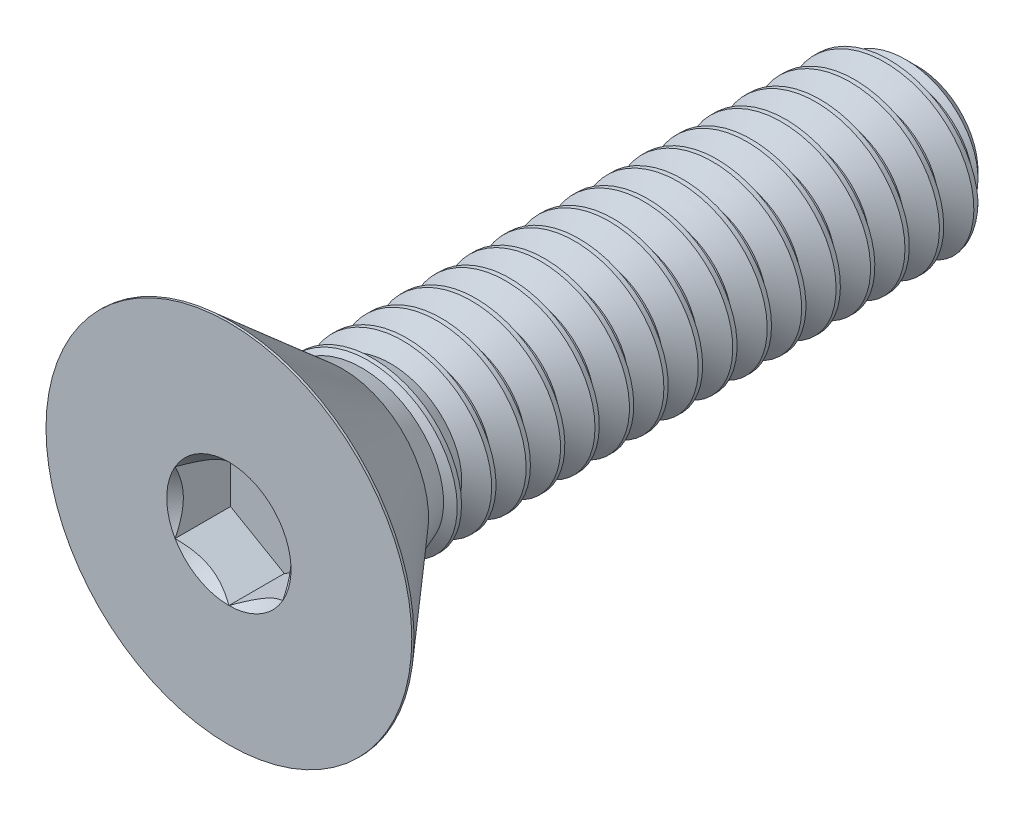
SolidWorks part; units mm, degrees
material "Plain Carbon Steel"
ref_plane "Front Plane" through (0, 0, 0) normal (0, 0, 1) x (1, 0, 0)
ref_plane "Top Plane" through (0, 0, 0) normal (0, 1, 0) x (1, 0, 0)
ref_plane "Right Plane" through (0, 0, 0) normal (1, 0, 0) x (0, 0, -1)
sketch "Sketch1" plane through (0, 0, 0) normal (1, 0, 0) x (0, 0, -1)
  line L0 (-12.7, 0) -> (12.7, 0) construction
  line L1 (-12.7, 0) -> (-12.7, 6.7437)
  line L2 (-12.7, 6.7437) -> (-12.6182, 6.7437)
  line L3 (-12.6182, 6.7437) -> (-8.6106, 3.2599)
  line L4 (-12.6182, -6.7437) -> (-8.6106, -3.2599)
  line L5 (12.7, 0) -> (12.7, 3.175)
  line L6 (12.7, 3.175) -> (-8.6106, 3.175)
  line L7 (11.7475, 3.175) -> (12.7, 2.2225)
  line L8 (12.6206, 3.3125) -> (13.2556, 2.2126) construction
  line L9 (13.2556, 2.2126) -> (13.8906, 3.3125) construction
  line L10 (13.8906, 3.3125) -> (12.6206, 3.3125) construction
  line L11 (12.6603, 3.2437) -> (13.8509, 3.2437)
  line L12 (13.8509, 3.2437) -> (13.335, 2.3501)
  line L13 (13.335, 2.3501) -> (13.1762, 2.3501)
  line L14 (13.1762, 2.3501) -> (12.6603, 3.2437)
  line L15 (13.2556, 2.3501) -> (13.2556, 2.2126) construction
  line L16 (12.7, 3.175) -> (13.8113, 3.175) construction
  line L17 (13.2556, 3.3125) -> (13.2556, 3.175) construction
  line L18 (12.7, -3.175) -> (-8.6106, -3.175)
  arc A0 (-8.6106, 3.2599) -> (-8.3834, 3.175) centre (-8.3834, 3.5213) ccw
  point P2 (0, 0)
  point P23 (-10.6553, 0)
  point P27 (13.2556, 3.2437)
  point P30 (10.795, -3.175)
  point P31 (-8.6106, 6.7437)
  point P33 (-8.6106, -6.7437)
  point P34 (-12.6182, -6.7437)
  point P35 (-12.7, 6.7437)
  dimension "Length" = 25.4
  dimension "Head Height" = 4.0894
  dimension "Head Diameter" = 13.4874
  dimension "Countersink Angle" = 82
  dimension "Screw Size Decimal Equivalent" = 6.35
  dimension "Pitch" = 1.27
  dimension "D4" = 0.1588
  dimension "D3" = 45
  dimension "D5" = 0.9525
  dimension "D6" = 2.0447
  dimension "D1" = 1.905
  dimension "D7" = 0.0818
sketch "Sketch8" plane through (0, 0, 0) normal (0, 0, 1) x (1, 0, 0)
  line L1 (0, 2.2914) -> (-1.9844, 1.1457)
  line L2 (-1.9844, 1.1457) -> (-1.9844, -1.1457)
  line L3 (-1.9844, -1.1457) -> (0, -2.2914)
  line L4 (0, -2.2914) -> (1.9844, -1.1457)
  line L5 (1.9844, -1.1457) -> (1.9844, 1.1457)
  line L6 (1.9844, 1.1457) -> (0, 2.2914)
  circle A0 centre (0, 0) radius 1.9844 construction
  dimension "Drive Size" = 3.9688
sketch "Sketch2" plane through (0, 0, 0) normal (1, 0, 0) x (0, 0, -1)
  line L0 (-12.6182, 6.7437) -> (-8.6106, 3.2599) construction
  line L1 (-12.7, 0) -> (-12.7, 6.7437) construction
  line L2 (-12.6182, 6.7437) -> (-8.5129, 3.175)
  line L3 (-12.7, 0) -> (-12.7, 6.7437)
  line L4 (-12.7, 6.7437) -> (-12.6182, 6.7437) construction
  line L5 (-12.7, 6.7437) -> (-12.6182, 6.7437)
  line L6 (-8.5129, 3.175) -> (11.7475, 3.175)
  line L7 (11.7475, 3.175) -> (12.7, 2.2225)
  line L8 (12.7, 2.2225) -> (12.7, 0)
  line L9 (12.7, 0) -> (-12.7, 0)
revolve "Revolve1" add sketch "Sketch2" angle 360 about L9
sketch "Sketch9" plane through (0, 0, 12.7) normal (0, 0, 1) x (1, 0, 0)
  line L0 (1.9844, -1.1457) -> (1.9844, 1.1457) construction
  line L1 (0, -2.2914) -> (1.9844, -1.1457) construction
  line L2 (-1.9844, -1.1457) -> (0, -2.2914) construction
  line L3 (-1.9844, 1.1457) -> (-1.9844, -1.1457) construction
  line L4 (0, 2.2914) -> (-1.9844, 1.1457) construction
  line L5 (1.9844, 1.1457) -> (0, 2.2914) construction
  line L6 (1.9844, -1.1457) -> (1.9844, 1.1457)
  line L7 (0, -2.2914) -> (1.9844, -1.1457)
  line L8 (-1.9844, -1.1457) -> (0, -2.2914)
  line L9 (-1.9844, 1.1457) -> (-1.9844, -1.1457)
  line L10 (0, 2.2914) -> (-1.9844, 1.1457)
  line L11 (1.9844, 1.1457) -> (0, 2.2914)
sketch "Sketch10" plane through (0, 0, 12.7) normal (0, 0, 1) x (1, 0, 0)
  circle A0 centre (0, 0) radius 2.2914
extrude "Cut-Extrude2" cut sketch "Sketch10" against normal up to vertex (2.0447 mm away) draft 45 up to point (0, 0, 10.6553)
extrude "Cut-Extrude1" cut sketch "Sketch9" against normal up to vertex (2.0447 mm away) up to point (0, 0, 10.6553)
ref_plane "Plane1" through (0, 0, 8.5129) normal (0, 0, 1) x (1, 0, 0)
split "Split1" trim tools "Plane1" bodies to split 111 resulting bodies 105 106
sketch "Sketch3" plane through (0, 0, -12.7) normal (0, 0, -1) x (-1, 0, 0)
  circle A0 centre (0, 0) radius 3.175 construction
  circle A1 centre (0, 0) radius 3.175
curve "Helix/Spiral1" pitch 1.27 height 25.4 radius 3.175 centre (0, 0, -12.7) axis (0, 0, 1) start towards (0, 1, 0)
sketch "Sketch4" plane through (0, 0, 0) normal (1, 0, 0) x (0, 0, -1)
  line L0 (12.6603, 3.2437) -> (13.8509, 3.2437) construction
  line L1 (13.1762, 2.3501) -> (12.6603, 3.2437) construction
  line L2 (13.335, 2.3501) -> (13.1762, 2.3501) construction
  line L3 (13.8509, 3.2437) -> (13.335, 2.3501) construction
  line L4 (12.6603, 3.2437) -> (13.8509, 3.2437)
  line L5 (13.1762, 2.3501) -> (12.6603, 3.2437)
  line L6 (13.335, 2.3501) -> (13.1762, 2.3501)
  line L7 (13.8509, 3.2437) -> (13.335, 2.3501)
sweep "Cut-Sweep1" cut profiles "Sketch4" path "Helix/Spiral1" align with end faces yes
sketch "Sketch7" plane through (0, 0, 8.5129) normal (0, 0, 1) x (1, 0, 0)
  circle A0 centre (0, 0) radius 3.175
extrude "Boss-Extrude2" add sketch "Sketch7" against normal up to next (21.2129 mm away) draft 20
equation "\"D4@Sketch1\" = \"Pitch@Sketch1\" / 8"
equation "\"D5@Sketch1\"=\"Pitch@Sketch1\"*0.75"
equation "\"D4@Helix/Spiral1\"=\"Pitch@Sketch1\""
equation "\"D3@Helix/Spiral1\"=\"Length@Sketch1\""
equation "\"D6@Sketch1\"=\"Head Height@Sketch1\"/2"
equation "\"D1@Sketch1\"=\"Pitch@Sketch1\"*1.5"
equation "\"D7@Sketch1\"=\"Head Height@Sketch1\"*0.02"
